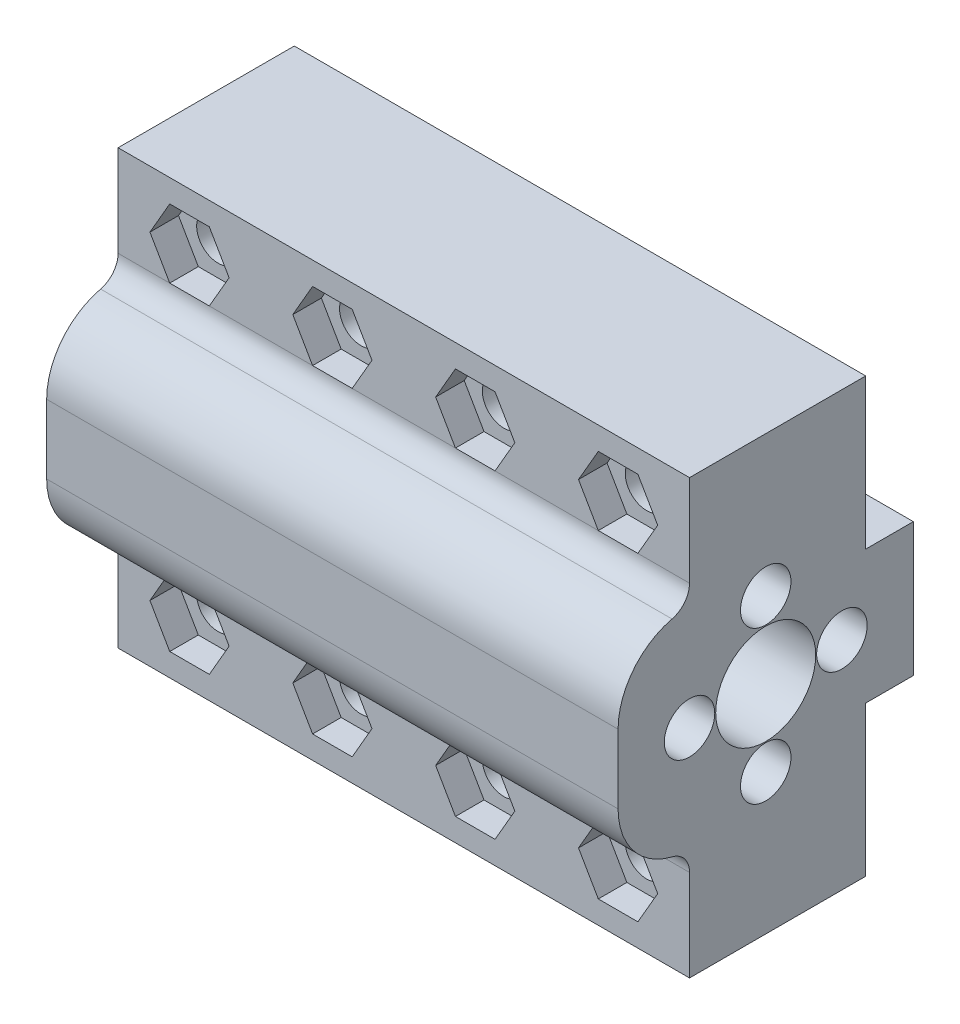
SolidWorks part; units mm, degrees
ref_plane "Front Plane" through (0, 0, 0) normal (0, 0, 1) x (1, 0, 0)
ref_plane "Top Plane" through (0, 0, 0) normal (0, 1, 0) x (1, 0, 0)
ref_plane "Right Plane" through (0, 0, 0) normal (1, 0, 0) x (0, 0, -1)
sketch "Sketch2" plane through (0, 0, 0) normal (1, 0, 0) x (0, 0, -1)
  line L0 (-15.5, 0) -> (15.5, 0) construction
  line L13 (-15.5, -22.75) -> (15.5, -22.75)
  line L18 (-15.5, -22.75) -> (-15.5, 22.75)
  line L19 (-15.5, 22.75) -> (15.5, 22.75)
  line L20 (15.5, -22.75) -> (15.5, 22.75)
  line L21 (-15.5, -22.75) -> (15.5, 22.75) construction
  line L22 (-15.5, 22.75) -> (15.5, -22.75) construction
  line L23 (15.5, 22.75) -> (10.5, 22.75)
  line L24 (15.5, 22.75) -> (15.5, 7)
  line L25 (15.5, 7) -> (10.5, 7)
  line L26 (10.5, 22.75) -> (10.5, 7)
  line L27 (15.5, -7) -> (10.5, -7)
  line L28 (10.5, -22.75) -> (10.5, -7)
  line L29 (15.5, -22.75) -> (10.5, -22.75)
  line L30 (15.5, -22.75) -> (15.5, -7)
  circle A1 centre (0, 0) radius 5.25
  dimension "D1" = 31
  dimension "D8" = 10.5
  dimension "D2" = 15.75
  dimension "D3" = 5
  dimension "D5" = 45.5
extrude "Boss-Extrude1" add sketch "Sketch2" along normal mid plane 60 contours L13 L28 L27 L20 L25 L26 L19 L18 A1 region at (0, 0, 14.9494)
sketch "Sketch4" plane through (-30, 0, 0) normal (-1, 0, 0) x (0, 0, 1)
  circle A0 centre (0, 0) radius 11.5
  dimension "D1" = 23
extrude "Cut-Extrude1" cut sketch "Sketch4" against normal blind 30
sketch "Sketch5" plane through (0, 0, 0) normal (-1, 0, 0) x (0, 0, 1)
  line L0 (0, 0) -> (0, 11.5) construction
  circle A0 centre (0, 0) radius 11.5 construction
  circle A1 centre (0, 8) radius 1.75
  circle A2 centre (8, 0) radius 1.75
  circle A3 centre (0, -8) radius 1.75
  circle A4 centre (-8, 0) radius 1.75
  point P17 (0, 0)
  dimension "D1" = 3.5
  dimension "D2" = 8
  dimension "D4" = 8
  dimension "D5" = 8
  dimension "D3" = 4
extrude "Cut-Extrude2" cut sketch "Sketch5" against normal up to next
sketch "Sketch6" plane through (30, 0, 0) normal (1, 0, 0) x (0, 0, -1)
  circle A0 centre (0, 8) radius 2.65
  circle A1 centre (8, 0) radius 2.65
  circle A2 centre (0, -8) radius 2.65
  circle A3 centre (-8, 0) radius 2.65
  point P12 (0, 0)
  dimension "D1" = 5.3
  dimension "D3" = 8
  dimension "D4" = 8
  dimension "D2" = 4
extrude "Cut-Extrude3" cut sketch "Sketch6" against normal blind 5.3
sketch "Sketch8" plane through (0, 0, 15.5) normal (0, 0, 1) x (1, 0, 0)
  line L0 (-30, 0) -> (30, 0) construction
  line L1 (-30, -22.75) -> (-30, 22.75) construction
  line L2 (30, -22.75) -> (30, 22.75) construction
  line L4 (30, 22.75) -> (-30, 22.75) construction
  circle A0 centre (-22.5, 16.75) radius 2.25
  circle A1 centre (-7.5, 16.75) radius 2.25
  circle A2 centre (7.5, 16.75) radius 2.25
  circle A3 centre (22.5, 16.75) radius 2.25
  circle A4 centre (22.5, -16.75) radius 2.25
  circle A5 centre (7.5, -16.75) radius 2.25
  circle A6 centre (-7.5, -16.75) radius 2.25
  circle A7 centre (-22.5, -16.75) radius 2.25
  dimension "D1" = 6
  dimension "D2" = 7.5
  dimension "D3" = 4.5
  dimension "D5" = 15
  dimension "D4" = 4
extrude "Cut-Extrude4" cut sketch "Sketch8" against normal up to next
sketch "Sketch10" plane through (30, 0, 0) normal (1, 0, 0) x (0, 0, -1)
  line L0 (-15.5, 0) -> (15.5, 0) construction
  line L5 (-15.5, 22.75) -> (-8, 22.75)
  line L6 (-15.5, 22.75) -> (-15.5, 10.75)
  line L7 (-15.5, 10.75) -> (-8, 10.75)
  line L8 (-8, 22.75) -> (-8, 10.75)
  line L9 (-15.5, -22.75) -> (-15.5, 22.75) construction
  line L10 (15.5, -7) -> (15.5, 7) construction
  line L11 (-15.5, -10.75) -> (-8, -10.75)
  line L12 (-8, -22.75) -> (-8, -10.75)
  line L13 (-15.5, -22.75) -> (-8, -22.75)
  line L14 (-15.5, -22.75) -> (-15.5, -10.75)
  dimension "D1" = 12
  dimension "D2" = 7.5
extrude "Cut-Extrude6" cut sketch "Sketch10" against normal up to next
sketch "Sketch9" plane through (0, 0, 8) normal (0, 0, 1) x (1, 0, 0)
  line L0 (-3.3431, 16.75) -> (-5.4215, 20.35)
  line L1 (-18.3431, 16.75) -> (-20.4215, 20.35)
  line L2 (-20.4215, 20.35) -> (-24.5785, 20.35)
  line L3 (-24.5785, 20.35) -> (-26.6569, 16.75)
  line L4 (-26.6569, 16.75) -> (-24.5785, 13.15)
  line L5 (-24.5785, 13.15) -> (-20.4215, 13.15)
  line L6 (-20.4215, 13.15) -> (-18.3431, 16.75)
  line L7 (-5.4215, 20.35) -> (-9.5785, 20.35)
  line L8 (-9.5785, 20.35) -> (-11.6569, 16.75)
  line L9 (-11.6569, 16.75) -> (-9.5785, 13.15)
  line L10 (-9.5785, 13.15) -> (-5.4215, 13.15)
  line L11 (-5.4215, 13.15) -> (-3.3431, 16.75)
  line L12 (11.6569, 16.75) -> (9.5785, 20.35)
  line L13 (9.5785, 20.35) -> (5.4215, 20.35)
  line L14 (5.4215, 20.35) -> (3.3431, 16.75)
  line L15 (3.3431, 16.75) -> (5.4215, 13.15)
  line L16 (5.4215, 13.15) -> (9.5785, 13.15)
  line L17 (9.5785, 13.15) -> (11.6569, 16.75)
  line L18 (26.6569, 16.75) -> (24.5785, 20.35)
  line L19 (24.5785, 20.35) -> (20.4215, 20.35)
  line L20 (20.4215, 20.35) -> (18.3431, 16.75)
  line L21 (18.3431, 16.75) -> (20.4215, 13.15)
  line L22 (20.4215, 13.15) -> (24.5785, 13.15)
  line L23 (24.5785, 13.15) -> (26.6569, 16.75)
  line L24 (-30, 0) -> (30, 0) construction
  line L25 (-30, -10.75) -> (-30, 10.75) construction
  line L26 (30, -10.75) -> (30, 10.75) construction
  line L27 (24.5785, -13.15) -> (26.6569, -16.75)
  line L28 (20.4215, -13.15) -> (24.5785, -13.15)
  line L29 (18.3431, -16.75) -> (20.4215, -13.15)
  line L30 (20.4215, -20.35) -> (18.3431, -16.75)
  line L31 (24.5785, -20.35) -> (20.4215, -20.35)
  line L32 (26.6569, -16.75) -> (24.5785, -20.35)
  line L33 (9.5785, -13.15) -> (11.6569, -16.75)
  line L34 (5.4215, -13.15) -> (9.5785, -13.15)
  line L35 (3.3431, -16.75) -> (5.4215, -13.15)
  line L36 (5.4215, -20.35) -> (3.3431, -16.75)
  line L37 (9.5785, -20.35) -> (5.4215, -20.35)
  line L38 (11.6569, -16.75) -> (9.5785, -20.35)
  line L39 (-5.4215, -13.15) -> (-3.3431, -16.75)
  line L40 (-9.5785, -13.15) -> (-5.4215, -13.15)
  line L41 (-11.6569, -16.75) -> (-9.5785, -13.15)
  line L42 (-9.5785, -20.35) -> (-11.6569, -16.75)
  line L43 (-5.4215, -20.35) -> (-9.5785, -20.35)
  line L44 (-20.4215, -13.15) -> (-18.3431, -16.75)
  line L45 (-24.5785, -13.15) -> (-20.4215, -13.15)
  line L46 (-26.6569, -16.75) -> (-24.5785, -13.15)
  line L47 (-24.5785, -20.35) -> (-26.6569, -16.75)
  line L48 (-20.4215, -20.35) -> (-24.5785, -20.35)
  line L49 (-18.3431, -16.75) -> (-20.4215, -20.35)
  line L50 (-3.3431, -16.75) -> (-5.4215, -20.35)
  circle A0 centre (-22.5, 16.75) radius 3.6 construction
  circle A1 centre (-22.5, -16.75) radius 3.6 construction
  dimension "D1" = 7.2
  dimension "D2" = 3.6
  dimension "D3" = 15
extrude "Cut-Extrude5" cut sketch "Sketch9" against normal blind 3
fillet "Fillet2" radius 2.4 2 edges at (0, -10.75, 8) (0, 10.75, 8)
fillet "Fillet3" radius 7.4 2 edges at (0, -10.75, 15.5) (0, 10.75, 15.5)
